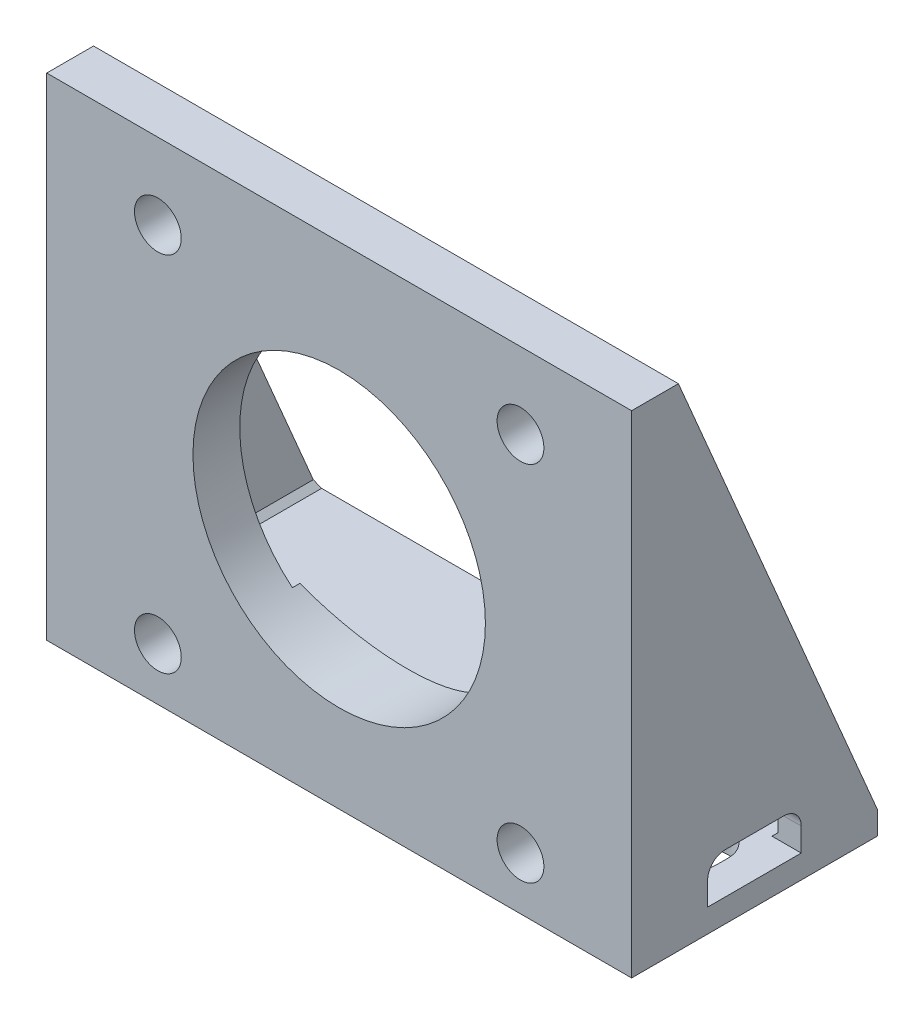
SolidWorks part; units mm, degrees
ref_plane "Front Plane" through (0, 0, 0) normal (0, 0, 1) x (1, 0, 0)
ref_plane "Top Plane" through (0, 0, 0) normal (0, 1, 0) x (1, 0, 0)
ref_plane "Right Plane" through (0, 0, 0) normal (1, 0, 0) x (0, 0, -1)
sketch "Sketch1" plane through (0, 0, 0) normal (0, 1, 0) x (1, 0, 0)
  line L0 (25, 21) -> (25, 0) construction
  line L1 (0, 0) -> (50, 0)
  line L2 (0, 0) -> (0, 21)
  line L3 (0, 21) -> (50, 21)
  line L4 (50, 0) -> (50, 21)
  line L5 (5, 11) -> (5, 10) construction
  line L6 (7.25, 11) -> (7.25, 10)
  line L7 (2.75, 11) -> (2.75, 10)
  line L8 (45, 11) -> (45, 10) construction
  line L9 (42.75, 11) -> (42.75, 10)
  line L10 (47.25, 11) -> (47.25, 10)
  line L11 (25, 16) -> (25, 15) construction
  line L12 (27.25, 16) -> (27.25, 15)
  line L13 (22.75, 16) -> (22.75, 15)
  arc A2 (7.25, 11) -> (2.75, 11) centre (5, 11) ccw
  arc A3 (2.75, 10) -> (7.25, 10) centre (5, 10) ccw
  arc A4 (42.75, 11) -> (47.25, 11) centre (45, 11) cw
  arc A5 (47.25, 10) -> (42.75, 10) centre (45, 10) cw
  arc A6 (27.25, 16) -> (22.75, 16) centre (25, 16) ccw
  arc A7 (22.75, 15) -> (27.25, 15) centre (25, 15) ccw
  point P7 (5, 10.5)
  point P16 (45, 10.5)
  point P23 (25, 15.5)
  dimension "D4" = 2.25
  dimension "D7" = 2.25
  dimension "D1" = 50
  dimension "D2" = 10
  dimension "D3" = 11
  dimension "D5" = 20
  dimension "D6" = 21
  dimension "D8" = 1
  dimension "D9" = 5
extrude "Base" add sketch "Sketch1" along normal blind 2
sketch "Sketch2" plane through (0, 0, 0) normal (0, 0, 1) x (1, 0, 0)
  line L0 (50, 2) -> (50, 0) construction
  line L1 (0, 0) -> (50, 0)
  line L2 (0, 0) -> (0, 42)
  line L3 (0, 42) -> (50, 42)
  line L4 (50, 0) -> (50, 42)
  line L5 (25, 42) -> (25, 0) construction
  circle A0 centre (9.5, 35.5) radius 2
  circle A1 centre (9.5, 4.5) radius 2
  circle A2 centre (40.5, 4.5) radius 2
  circle A3 centre (40.5, 35.5) radius 2
  circle A4 centre (25, 20) radius 12.5
  dimension "D2" = 4
  dimension "D5" = 25
  dimension "D1" = 42
  dimension "D3" = 31
  dimension "D4" = 31
  dimension "D6" = 22
  dimension "D7" = 25
  dimension "D8" = 15.5
  dimension "D9" = 15.5
extrude "Encaixe Motor" add sketch "Sketch2" against normal blind 4
sketch "Sketch3" plane through (50, 0, 0) normal (1, 0, 0) x (0, 0, -1)
  line L0 (21, 2) -> (4, 42)
  line L1 (4, 42) -> (4, 2)
  line L2 (4, 2) -> (6.5, 2)
  line L3 (10, 2) -> (10, 0) construction
  line L5 (6.5, 2) -> (6.5, 4)
  line L6 (8, 5.5) -> (13, 5.5)
  line L7 (14.5, 2) -> (14.5, 4)
  line L8 (11, 2) -> (11, 0) construction
  line L9 (14.5, 2) -> (21, 2)
  arc A0 (14.5, 4) -> (13, 5.5) centre (13, 4) ccw
  arc A1 (8, 5.5) -> (6.5, 4) centre (8, 4) ccw
  point P16 (14.5, 5.5)
  dimension "D4" = 1.5
  dimension "D1" = 3.5
  dimension "D2" = 3.5
  dimension "D3" = 3.5
extrude "Laterais - Bloco" add sketch "Sketch3" against normal up to surface (50 mm away)
sketch "Sketch4" plane through (0, 0, -21) normal (0, 0, -1) x (-1, 0, 0)
  line L0 (-50, 2) -> (0, 2) construction
  line L1 (-48, 2) -> (-2, 2)
  line L2 (-48, 2) -> (-48, 42)
  line L3 (-48, 42) -> (-2, 42)
  line L4 (-2, 2) -> (-2, 42)
  line L5 (-50, 42) -> (0, 42) construction
  line L6 (-50, 2) -> (-50, 42) construction
  line L7 (0, 42) -> (0, 2) construction
  dimension "D1" = 2
  dimension "D2" = 2
extrude "Laterais - Corte" cut sketch "Sketch4" against normal up to vertex
ref_plane "Plano de Referência" through (25, 0, 0) normal (-1, 0, 0) x (0, 0, 1)
sketch "Sketch5" plane through (25, 0, 0) normal (-1, 0, 0) x (0, 0, 1)
  line L0 (-4, 2) -> (-8, 2)
  line L1 (-7.75, 2) -> (-10, 2) construction
  line L2 (-8, 2) -> (-4, 12)
  line L3 (-4, 12) -> (-4, 2)
  line L4 (0, 0) -> (-21, 0) construction
  dimension "D1" = 4
  dimension "D2" = 12
extrude "Suporte Central" add sketch "Sketch5" along normal blind 8 and the other way blind 8
sketch "Sketch6" plane through (0, 0, -4) normal (0, 0, 1) x (1, 0, 0)
  circle A0 centre (25, 20) radius 12.5
extrude "Furo Motor Ø25" cut sketch "Sketch6" against normal through all
chamfer "Chanfros 1x45°" distance 0.5 angle 45 9 edges at (2, 2, -17.75) (2, 2, -5.25) (9.5, 2, -4) (17, 2, -6) (25, 2, -8) (33, 2, -6) (40.5, 2, -4) (48, 2, -5.25) (48, 2, -17.75)
chamfer "Chanfros 2x45°" distance 2 angle 45 2 edges at (48, 22.25, -4) (2, 22.25, -4)
